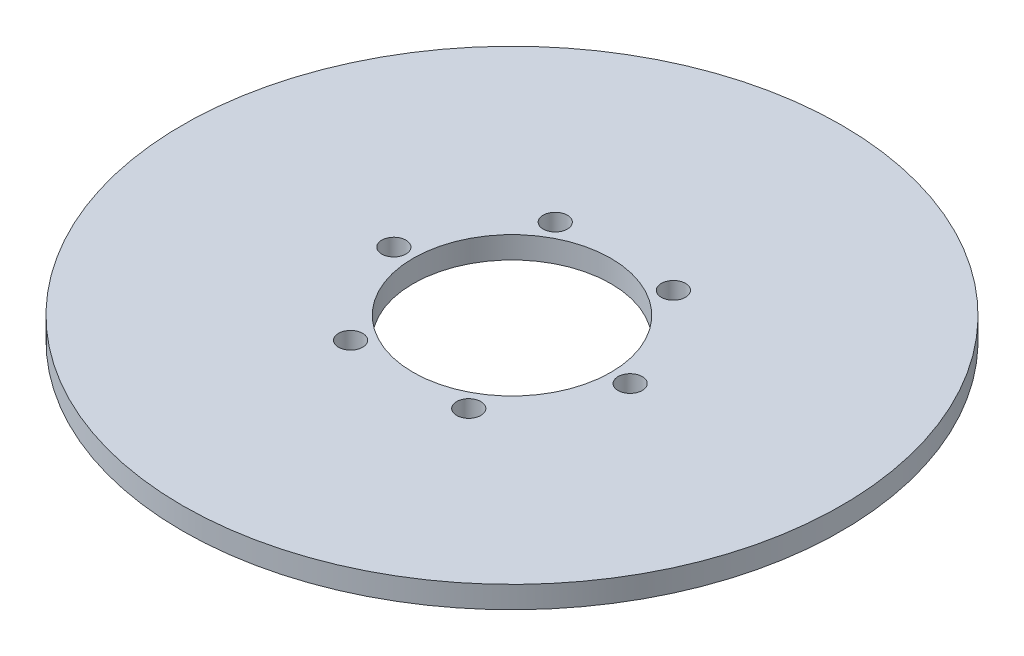
SolidWorks part; units mm, degrees
ref_plane "Front Plane" through (0, 0, 0) normal (0, 0, 1) x (1, 0, 0)
ref_plane "Top Plane" through (0, 0, 0) normal (0, 1, 0) x (1, 0, 0)
ref_plane "Right Plane" through (0, 0, 0) normal (1, 0, 0) x (0, 0, -1)
sketch "Sketch1" plane through (0, 0, 0) normal (0, 1, 0) x (1, 0, 0)
  circle A0 centre (0, 0) radius 75
  dimension "FLANGE_OD" = 150
extrude "Boss-Extrude1" add sketch "Sketch1" along normal blind 5
sketch "Sketch2" plane through (0, 0, 0) normal (0, 1, 0) x (1, 0, 0)
  circle A0 centre (0, 0) radius 22.5
  dimension "BORE_D" = 45
extrude "Cut-Extrude1" cut sketch "Sketch2" along normal through all
sketch "Sketch3" plane through (0, 5, 0) normal (0, 1, 0) x (1, 0, 0)
  circle A0 centre (0, 0) radius 26.8914 construction
  circle A1 centre (-26.8914, 0) radius 2.7529
  dimension "BOLT_D" = 5.5058
  dimension "BOLT_PCD" = 53.7828
extrude "Cut-Extrude2" cut sketch "Sketch3" against normal blind 4.4817
pattern_circular "CirPattern1" count 6 over 360 about axis through (0, 0, 0) along (0, 1, 0) of "Cut-Extrude2"
